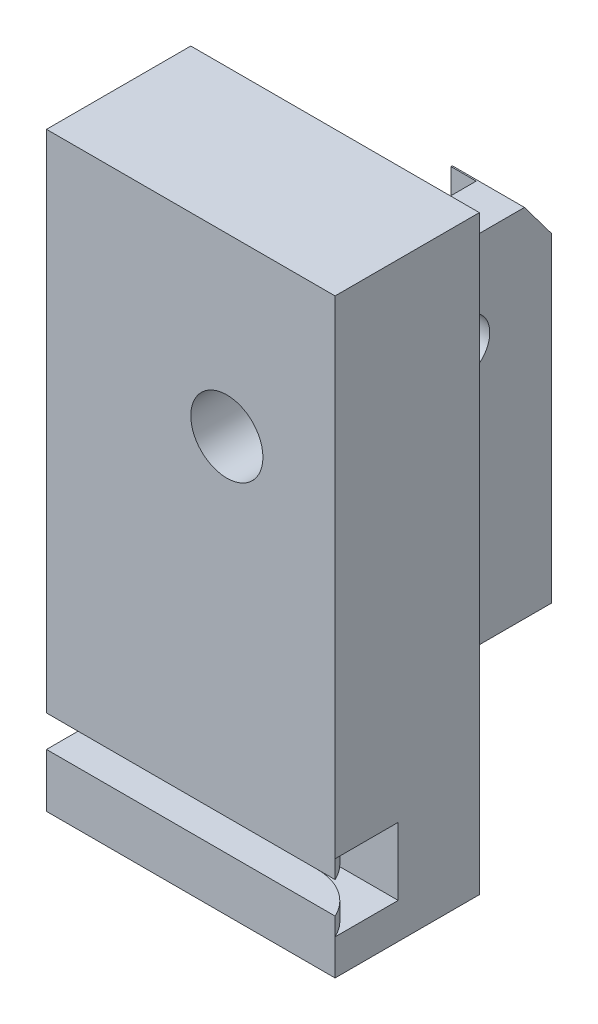
SolidWorks part; units mm, degrees
other "Markup1"
sketch "Sketch3" plane through (0, 0, 24) normal (-0.9768, -0.0702, 0.2026) x (0.2071, -0.0648, 0.9762)
ref_plane "Front Plane" through (0, 0, 0) normal (0, 0, 1) x (1, 0, 0)
ref_plane "Top Plane" through (0, 0, 0) normal (0, 1, 0) x (1, 0, 0)
ref_plane "Right Plane" through (0, 0, 0) normal (1, 0, 0) x (0, 0, -1)
sketch "ProfileSketch2" plane through (0, 0, 0) normal (0, 1, 0) x (1, 0, 0)
  line L0 (0, 0) -> (0, -24)
  line L1 (0, -24) -> (16, -24)
  line L5 (16, -16) -> (4, -16)
  line L6 (4, -16) -> (4, 0)
  line L7 (4, 0) -> (0, 0)
  line L8 (16, -16) -> (16, -24)
  dimension "D1" = 16
  dimension "D2" = 4
  dimension "D3" = 16
  dimension "D4" = 24
extrude "ProfileBoss-Extrude1" add sketch "ProfileSketch2" along normal blind 34.75
sketch "MicroSwitchHoleSketch3" plane through (0, 0, 0) normal (-1, 0, 0) x (0, 0, 1)
  line L1 (1.575, 19.75) -> (14.625, 19.75)
  line L2 (1.575, 19.75) -> (1.575, 7.7)
  line L3 (1.575, 7.7) -> (14.625, 7.7)
  line L4 (14.625, 19.75) -> (14.625, 7.7)
  line L5 (0, 34.75) -> (24, 34.75) construction
  line L6 (0, 34.75) -> (0, 0) construction
  dimension "D1" = 13.05
  dimension "D2" = 12.05
  dimension "D4" = 1.575
  dimension "D3" = 15
extrude "MicroSwitchHoleCut-Extrude1" cut sketch "MicroSwitchHoleSketch3" against normal blind 1.4
sketch "MicroSwitchHoleSketch4" plane through (1.4, 0, 0) normal (-1, 0, 0) x (0, 0, 1)
  line L0 (1.575, 19.75) -> (1.575, 7.7) construction
  line L1 (14.625, 7.7) -> (14.625, 19.75) construction
  line L2 (1.575, 7.7) -> (14.625, 7.7) construction
  circle A0 centre (4.925, 14.7) radius 1.5
  circle A1 centre (11.375, 14.7) radius 1.5
  dimension "D1" = 3
  dimension "D2" = 3.35
  dimension "D3" = 3.25
  dimension "D4" = 7
extrude "MicroSwitchHoleCut-Extrude2" cut sketch "MicroSwitchHoleSketch4" against normal blind 3
sketch "LongWireChannelSketch7" plane through (0, 0, 0) normal (-1, 0, 0) x (0, 0, 1)
  line L0 (24, 4.725) -> (22.25, 4.725)
  line L1 (24, 34.75) -> (24, 0) construction
  line L2 (22.25, 4.725) -> (22.25, 5.725)
  line L3 (22.25, 5.725) -> (20.5, 5.725)
  line L4 (20.5, 5.725) -> (20.5, 1.975)
  line L5 (20.5, 1.975) -> (22.25, 1.975)
  line L6 (22.25, 1.975) -> (22.25, 2.975)
  line L7 (22.25, 2.975) -> (24, 2.975)
  line L8 (24, 2.975) -> (24, 4.725)
  line L9 (1.575, 7.7) -> (14.625, 7.7) construction
  dimension "D1" = 1.75
  dimension "D2" = 3.75
  dimension "D3" = 1.75
  dimension "D4" = 1.975
extrude "LongWireChannelCut-Extrude5" cut sketch "LongWireChannelSketch7" against normal through all
sketch "ShortWireChannelSketch8" plane through (0, 0, 0) normal (-1, 0, 0) x (0, 0, 1)
  line L0 (6.125, 7.7) -> (6.125, 1.975)
  line L1 (6.125, 1.975) -> (20.5, 1.975)
  line L2 (20.5, 5.725) -> (20.5, 1.975) construction
  line L3 (20.5, 1.975) -> (20.5, 5.725)
  line L4 (20.5, 5.725) -> (9.875, 5.725)
  line L5 (9.875, 5.725) -> (9.875, 7.7)
  line L6 (1.575, 7.7) -> (14.625, 7.7) construction
  line L7 (9.875, 7.7) -> (6.125, 7.7)
  line L8 (22.25, 5.725) -> (20.5, 5.725) construction
  line L11 (20.5, 1.975) -> (22.25, 1.975) construction
  line L12 (1.575, 7.7) -> (14.625, 7.7) construction
  line L13 (0, 34.75) -> (0, 0) construction
  dimension "D1" = 6.125
extrude "ShortWireChannelCut-Extrude6" cut sketch "ShortWireChannelSketch8" against normal blind 1.4
fillet "Fillet1" radius 2.2 1 edges at (1.4, 3.85, 20.5)
sketch "LinearRaukHoleSketch1" plane through (0, 0, 24) normal (0, 0, 1) x (1, 0, 0)
  line L1 (0, 0) -> (16, 0) construction
  line L2 (16, 34.75) -> (16, 4.725) construction
  circle A0 centre (10, 23) radius 2
  dimension "D1" = 4
  dimension "D3" = 23
  dimension "D2" = 6
extrude "LinearRailHoleCut-Extrude1" cut sketch "LinearRaukHoleSketch1" against normal through all
fillet "Fillet2" radius 3 2 edges at (0.7, 5.725, 9.875) (0.7, 7.7, 6.125)
fillet "Fillet3" radius 3 2 edges at (16, 2.475, 22.25) (16, 5.225, 22.25)
sketch "Sketch2" plane through (0, 0, 24) normal (0, 0, 1) x (1, 0, 0)
  line L0 (16, 34.75) -> (16, 5.725) construction
  line L1 (0, 34.75) -> (16, 34.75)
  line L2 (0, 34.75) -> (0, 32.75)
  line L3 (0, 32.75) -> (16, 32.75)
  line L4 (16, 34.75) -> (16, 32.75)
  dimension "D1" = 2
extrude "KnotchCut-Extrude2" cut sketch "Sketch2" against normal blind 8
sketch "DeeperCutSketch4" plane through (0, 0, 0) normal (-1, 0, 0) x (0, 0, 1)
  line L0 (16, 34.75) -> (16, 32.75) construction
  line L1 (0, 34.75) -> (16, 34.75)
  line L2 (0, 34.75) -> (0, 19.75)
  line L3 (0, 19.75) -> (16, 19.75)
  line L4 (16, 34.75) -> (16, 19.75)
  line L5 (14.625, 19.75) -> (1.575, 19.75) construction
extrude "DeeperCut-Extrude1" cut sketch "DeeperCutSketch4" against normal through all
chamfer "Chamfer1" distance 2 distance2 1.5 1 edges at (2, 19.75, 0) first distance on face at (2, 9.875, 0)
equation "\"LinearRailWidth\"= 12mm'Spec"
equation "\"LinearRailHeight\"= 8mm'Spec"
equation "\"LinearRailHoleDiameter\"= 3.5mm'Spec"
equation "\"LinearRailHoleDistance\"= 25mm'Spec"
equation "\"LinearRailSupportNutWidth\"= 6.2mm"
equation "\"LinearRailSupportNutHoleDepth\"= \"LinearRailHeight\" / 4"
equation "\"M2HeatInsertDiameter\"= 3mm'Spec"
equation "\"M2HeatInsertHoleDepth\"= 3mm"
equation "\"MicroSwitchMountingHoleOffsetFromBottom\"= 1.5mm"
equation "\"MicroSwitchTerminalHeight\"= 3.5mm"
equation "\"MicroSwitchDepth\"= 2.8mm"
equation "\"MicroSwitchLength\" = 13.05mm"
equation "\"MicroSwitchHeight\"= 6.55mm"
equation "\"MicroSwitchMountingHoleOffsetFromSide\"= 3.35mm"
equation "\"D1@MicroSwitchHoleSketch3\" = \"MicroSwitchLength\""
equation "\"D2@MicroSwitchHoleSketch3\"=\"MicroSwitchMountingHoleHeight\""
equation "\"MicroSwitchExtraMountingHeight\"= 2mm"
equation "\"D1@MicroSwitchHoleCut-Extrude1\"=\"MicroSwitchDepth\" / 2"
equation "\"D1@MicroSwitchHoleSketch4\" = \"M2HeatInsertDiameter\""
equation "\"D2@MicroSwitchHoleSketch4\" = \"MicroSwitchMountingHoleOffsetFromSide\""
equation "\"D4@MicroSwitchHoleSketch4\" = \"MicroSwitchExtraMountingHeight\" + \"MicroSwitchTerminalHeight\" + \"MicroSwitchMountingHoleOffsetFromBottom\""
equation "\"D1@MicroSwitchHoleCut-Extrude2\" = \"M2HeatInsertHoleDepth\""
equation "\"XAxisMicroSwitchClampHeight\"= \"LinearRailWidth\" + \"LinearRailHeight\" / 2"
equation "\"XAxisMicroSwitchClampWidth\"= \"LinearRailHeight\" + \"LinearRailHeight\" + \"LinearRailHeight\""
equation "\"XAxisMicroSwitchClampDepth\"= \"LinearRailHeight\" * 2 + \"EndStopCableWidth\" + \"MakeDeeper\""
equation "\"M3HeatInsertHoleDiameter\"= 4mm'Spec"
equation "\"M3HeatInsertHoleDepth\"= 4.1mm"
equation "\"D1@ProfileBoss-Extrude1\"=\"XAxisMicroSwitchClampDepth\""
equation "\"MicroSwitchMountingHoleHeight\"= \"MicroSwitchExtraMountingHeight\" + \"MicroSwitchTerminalHeight\" + \"MicroSwitchHeight\""
equation "\"D4@LongWireChannelSketch7\"=( \"XAxisMicroSwitchClampDepth\" - \"MicroSwitchMountingHoleHeight\" - \"EndStopCableWidth\" - \"MakeDeeper\")  / 2"
equation "\"D1@ShortWireChannelSketch8\"=( \"XAxisMicroSwitchClampHeight\" - \"EndStopCableWidth\" )  / 2"
equation "\"D1@ShortWireChannelCut-Extrude6\"=\"MicroSwitchDepth\"/ 2"
equation "\"EndStopCableDepth\"= 1.75mm"
equation "\"EndStopCableWidth\"= 3.75mm"
equation "\"D1@LongWireChannelSketch7\"=\"EndStopCableDepth\""
equation "\"D2@LongWireChannelSketch7\"=\"EndStopCableWidth\""
equation "\"D3@LongWireChannelSketch7\"=\"EndStopCableDepth\""
equation "\"D1@ProfileSketch2\"=\"LinearRailHeight\" * 2"
equation "\"D2@ProfileSketch2\"=\"LinearRailHeight\"/2"
equation "\"D3@ProfileSketch2\"=\"XAxisMicroSwitchClampHeight\""
equation "\"D4@ProfileSketch2\"=\"XAxisMicroSwitchClampWidth\""
equation "\"D1@LinearRaukHoleSketch1\" = \"M3HeatInsertHoleDiameter\""
equation "\"D3@LinearRaukHoleSketch1\"=\"XAxisMicroSwitchClampHeight\" / 2 + \"MakeDeeper\""
equation "\"D2@LinearRaukHoleSketch1\"=\"LinearRailWidth\"/2"
equation "\"MakeDeeper\"= 15mm"
equation "\"D3@MicroSwitchHoleSketch3\"=\"MakeDeeper\""
